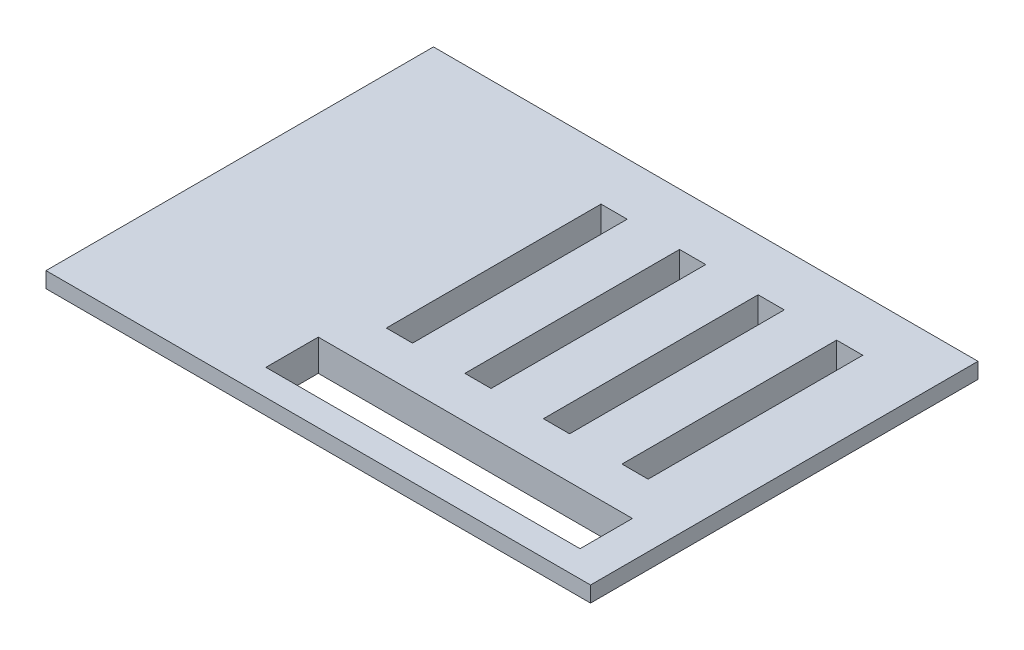
SolidWorks part; units mm, degrees
material "ABS"
ref_plane "Front Plane" through (0, 0, 0) normal (0, 0, 1) x (1, 0, 0)
ref_plane "Top Plane" through (0, 0, 0) normal (0, 1, 0) x (1, 0, 0)
ref_plane "Right Plane" through (0, 0, 0) normal (1, 0, 0) x (0, 0, -1)
sketch "Sketch1" plane through (0, 0, 0) normal (0, 1, 0) x (1, 0, 0)
  line L0 (-7, -5) -> (-7, 69)
  line L5 (0, 0) -> (90, 0)
  line L6 (0, 0) -> (0, 64)
  line L11 (0, 64) -> (90, 64)
  line L12 (90, 0) -> (90, 64)
  line L13 (-7, 69) -> (97, 69)
  line L14 (97, 69) -> (97, -5)
  line L15 (97, -5) -> (-7, -5)
  point P0 (0, 0)
  point P6 (0, 0)
  dimension "D1" = 64
  dimension "D2" = 90
  dimension "D3" = 7
  dimension "D4" = 7
  dimension "D5" = 5
  dimension "D6" = 5
extrude "Boss-Extrude1" add sketch "Sketch1" along normal blind 3 and the other way blind 3 contours L6 L5 L12 L11
extrude "Boss-Extrude3" add sketch "Sketch1<4>" along normal up to surface (3 mm away) up to face at (45, 3, -32)
sketch "Sketch1<4>" plane through (0, 0, 0) normal (0, 1, 0) x (1, 0, 0) same geometry as "Sketch1"
sketch "Sketch2" plane through (0, -3, 0) normal (0, -1, 0) x (1, 0, 0)
  line L0 (90, 0) -> (90, -64) construction
  line L1 (30, 0) -> (90, 0)
  line L2 (30, 0) -> (30, -10)
  line L3 (30, -10) -> (90, -10)
  line L4 (90, 0) -> (90, -10)
  dimension "D1" = 60
  dimension "D2" = 10
extrude "Cut-Extrude1" cut sketch "Sketch2" against normal through all both and the other way through all
sketch "Sketch3" plane through (0, 3, 0) normal (0, 1, 0) x (1, 0, 0)
  line L0 (97, 69) -> (-7, 69) construction
  line L1 (35, 59) -> (40, 59)
  line L2 (35, 59) -> (35, 18)
  line L3 (35, 18) -> (40, 18)
  line L4 (40, 59) -> (40, 18)
  line L5 (50, 59) -> (55, 59)
  line L6 (50, 59) -> (50, 18)
  line L7 (50, 18) -> (55, 18)
  line L8 (55, 59) -> (55, 18)
  line L9 (65, 59) -> (70, 59)
  line L10 (65, 59) -> (65, 18)
  line L11 (65, 18) -> (70, 18)
  line L12 (70, 59) -> (70, 18)
  line L13 (80, 59) -> (85, 59)
  line L14 (80, 59) -> (80, 18)
  line L15 (80, 18) -> (85, 18)
  line L16 (85, 59) -> (85, 18)
  line L17 (30, 10) -> (90, 10) construction
  line L18 (30, 10) -> (90, 10)
  line L19 (35, 18) -> (85, 18) construction
  point P20 (60, 18)
  point P22 (60, 10)
  dimension "D1" = 5
  dimension "D2" = 5
  dimension "D3" = 5
  dimension "D4" = 5
  dimension "D5" = 10
  dimension "D6" = 10
  dimension "D7" = 10
  dimension "D8" = 10
  dimension "D9" = 8
extrude "Cut-Extrude2" cut sketch "Sketch3" against normal through all contours L4 L1 L2 L3 | L8 L5 L6 L7 | L16 L13 L14 L15 | L10 L11 L12 L9 region at (37.5, 3, -38.5) region at (52.5, 3, -38.5) region at (82.5, 3, -38.5)
